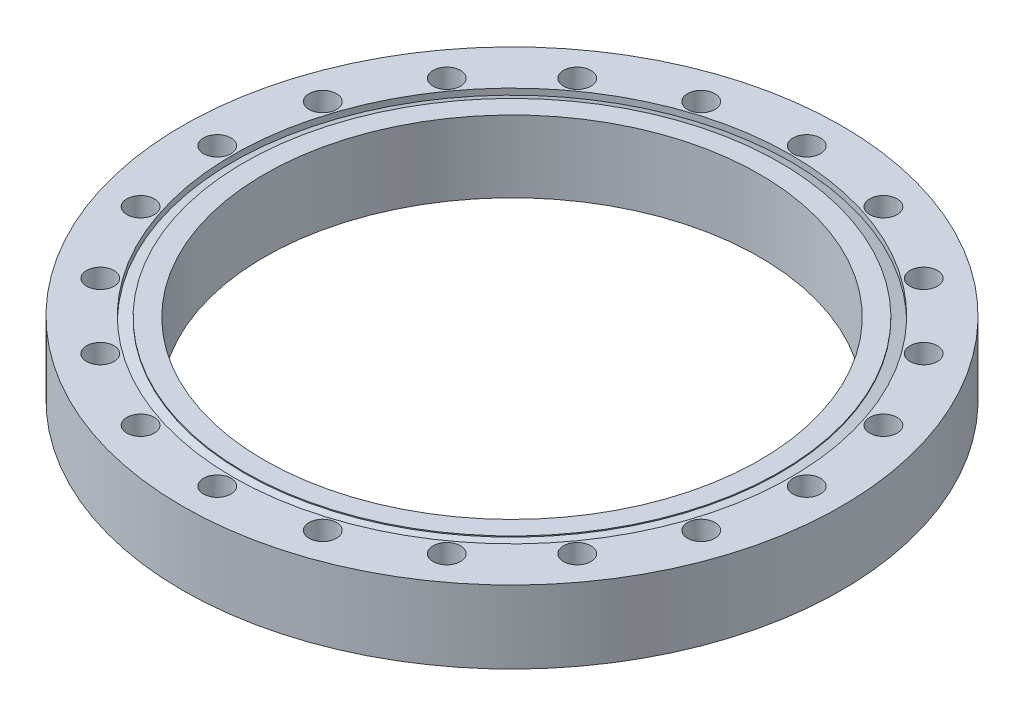
SolidWorks part; units mm, degrees
ref_plane "Front Plane" through (0, 0, 0) normal (0, 0, 1) x (1, 0, 0)
ref_plane "Top Plane" through (0, 0, 0) normal (0, 1, 0) x (1, 0, 0)
ref_plane "Right Plane" through (0, 0, 0) normal (1, 0, 0) x (0, 0, -1)
sketch "Sketch1" plane through (0, 0, 0) normal (0, 0, 1) x (1, 0, 0)
  line L0 (101.219, 11.176) -> (101.219, -11.176)
  line L2 (76.073, -11.176) -> (101.219, -11.176)
  line L3 (101.219, 11.176) -> (85.725, 11.176)
  line L4 (85.725, 11.176) -> (85.725, 9.2929)
  line L5 (85.725, 9.2929) -> (82.296, 10.541)
  line L6 (82.296, 10.541) -> (82.296, 10.8522)
  line L7 (0, 0) -> (101.219, 0) construction
  line L8 (0, 42.3692) -> (0, -30.2548) construction
  line L10 (0, -4.4144) -> (73.025, -4.4144) construction
  line L11 (76.073, 10.8522) -> (82.296, 10.8522)
  line L13 (76.073, -11.176) -> (76.073, 10.8522)
  dimension "D1" = 101.219
  dimension "D2" = 0.3112
  dimension "D3" = 22.352
  dimension "D4" = 20
  dimension "D5" = 85.725
  dimension "D6" = 76.073
  dimension "D8" = 0.635
  dimension "D10" = 6.223
revolve "Revolve1" add sketch "Sketch1" angle 360 about L8
sketch "Sketch2" plane through (0, 0, 0) normal (0, 0, 1) x (1, 0, 0)
  line L0 (0, 42.3692) -> (0, -30.2548) construction
  line L1 (90.5256, 11.176) -> (90.5256, -11.176)
  line L2 (101.219, 11.176) -> (85.725, 11.176) construction
  line L3 (76.073, -11.176) -> (101.219, -11.176) construction
  line L4 (90.5256, -11.176) -> (94.742, -11.176)
  line L5 (94.742, -11.176) -> (94.742, 11.176)
  line L6 (94.742, 11.176) -> (90.5256, 11.176)
  line L7 (90.5256, 40.326) -> (90.5256, -23.2947) construction
  dimension "D1" = 90.5256
  dimension "D2" = 4.2164
revolve "Cut-Revolve1" cut sketch "Sketch2" angle 360 about L7
ref_axis "Axis1" through (0, -33.886, 0) along (0, 1, 0)
pattern_circular "CirPattern1" count 20 over 360 about axis through (0, -33.886, 0) along (0, 1, 0) of "Cut-Revolve1"
